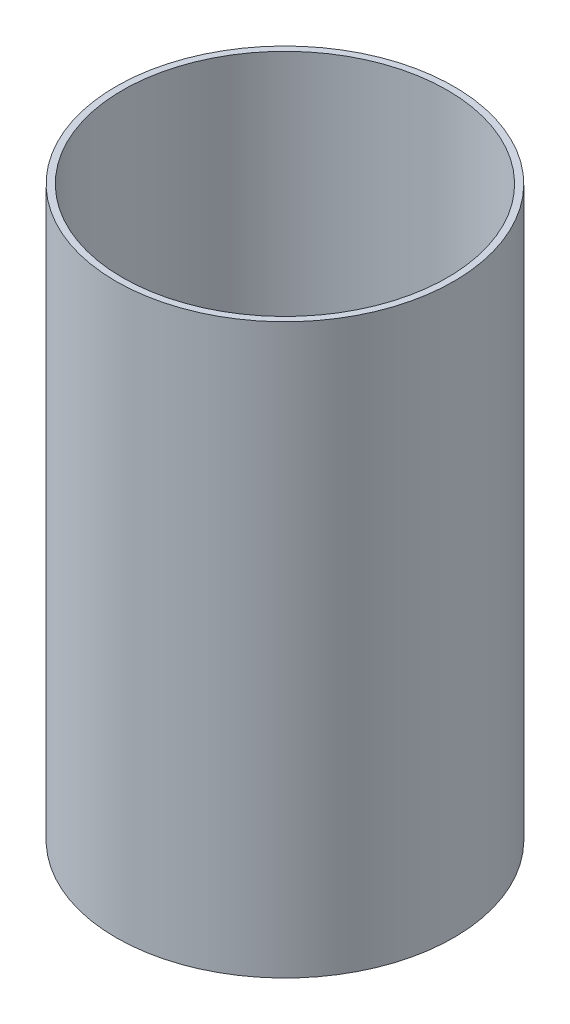
SolidWorks part; units mm, degrees
material "PTFE (general)"
ref_plane "Front Plane" through (0, 0, 0) normal (0, 0, 1) x (1, 0, 0)
ref_plane "Top Plane" through (0, 0, 0) normal (0, 1, 0) x (1, 0, 0)
ref_plane "Right Plane" through (0, 0, 0) normal (1, 0, 0) x (0, 0, -1)
ref_axis "Axis1" through (0, 55, 0) along (0, -1, 0)
sketch "Sketch2" plane through (0, 0, 0) normal (0, 0, 1) x (1, 0, 0)
  line L1 (-39.624, 0) -> (-38.1, 0)
  line L2 (-39.624, 0) -> (-39.624, -133.35)
  line L3 (-39.624, -133.35) -> (-38.1, -133.35)
  line L4 (-38.1, 0) -> (-38.1, -133.35)
  dimension "D2" = 1.524
revolve "Revolve1" add sketch "Sketch2" angle 360 about axis through (0, 55, 0) along (0, -1, 0)
equation "\"D2@Sketch2\"=\"LINER THICKNESS@Cryo Tank.Assembly\""
